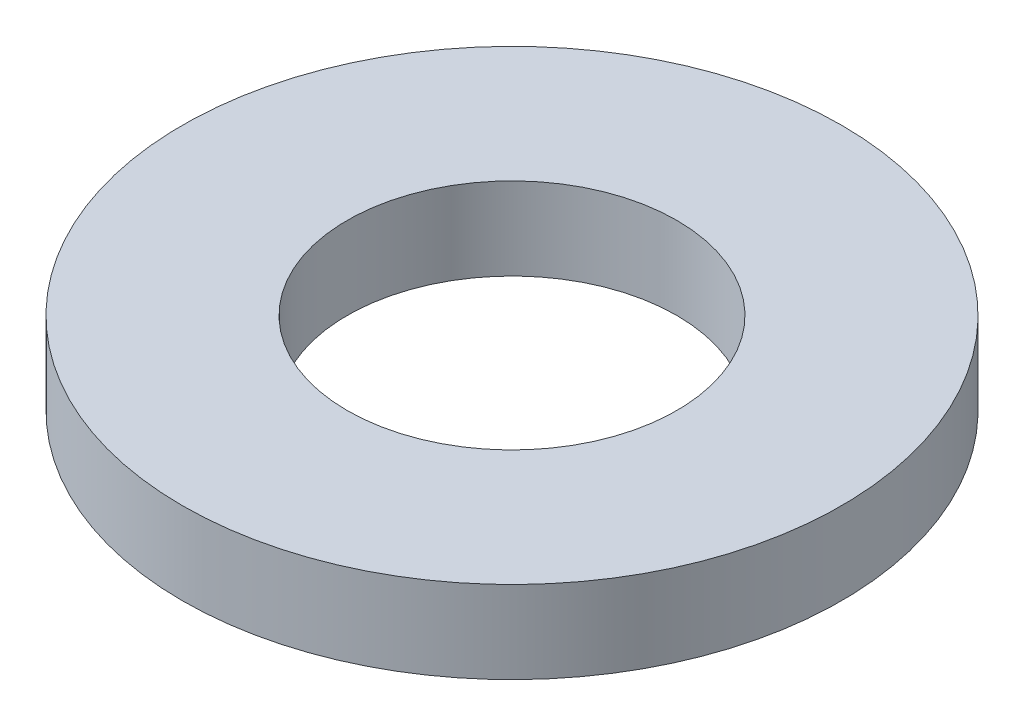
SolidWorks part; units mm, degrees
ref_plane "Front Plane" through (0, 0, 0) normal (0, 0, 1) x (1, 0, 0)
ref_plane "Top Plane" through (0, 0, 0) normal (0, 1, 0) x (1, 0, 0)
ref_plane "Right Plane" through (0, 0, 0) normal (1, 0, 0) x (0, 0, -1)
sketch "Sketch1" plane through (0, 0, 0) normal (0, 1, 0) x (1, 0, 0)
  circle A0 centre (0, 0) radius 40
  dimension "FLANGE_OD" = 80
extrude "Boss-Extrude1" add sketch "Sketch1" along normal blind 10
sketch "Sketch2" plane through (0, 0, 0) normal (0, 1, 0) x (1, 0, 0)
  circle A0 centre (0, 0) radius 20
  dimension "BORE_D" = 40
extrude "Cut-Extrude1" cut sketch "Sketch2" along normal through all
sketch "Sketch3" plane through (0, 10, 0) normal (0, 1, 0) x (1, 0, 0)
  circle A0 centre (0, 0) radius 15.1559 construction
  circle A1 centre (-15.1559, 0) radius 3.22
  dimension "BOLT_D" = 6.44
  dimension "BOLT_PCD" = 30.3118
extrude "Cut-Extrude2" cut sketch "Sketch3" against normal blind 8.1537 rebuild error yes
pattern_circular "CirPattern1" count 3 over 360 rebuild error yes
